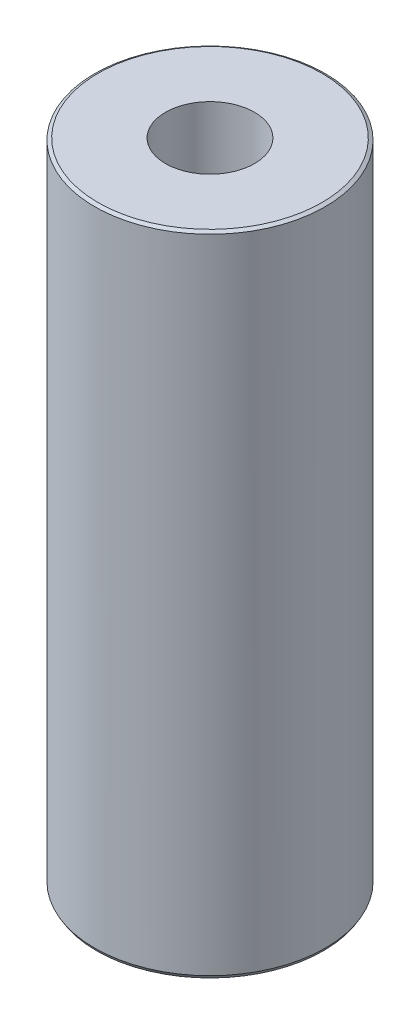
SolidWorks part; units mm, degrees
ref_plane "Front Plane" through (0, 0, 0) normal (0, 0, 1) x (1, 0, 0)
ref_plane "Top Plane" through (0, 0, 0) normal (0, 1, 0) x (1, 0, 0)
ref_plane "Right Plane" through (0, 0, 0) normal (1, 0, 0) x (0, 0, -1)
sketch "Sketch1" plane through (0, 0, 0) normal (0, 1, 0) x (1, 0, 0)
  circle A0 centre (0, 0) radius 22.5
  dimension "SHAFT_OD" = 45
extrude "Boss-Extrude1" add sketch "Sketch1" along normal blind 126.3228
sketch "Sketch2" plane through (0, 0, 0) normal (0, 1, 0) x (1, 0, 0)
  circle A0 centre (0, 0) radius 8.6848
  dimension "BORE_D" = 17.3696
extrude "Cut-Extrude1" cut sketch "Sketch2" along normal through all
chamfer "Chamfer1" distance 0.3746 angle 60 2 edges at (0, 126.3228, 22.5) (0, 0, 22.5) first distance on face at (0, 126.3228, 22.5) first distance on face at (0, 0, 8.6848)
